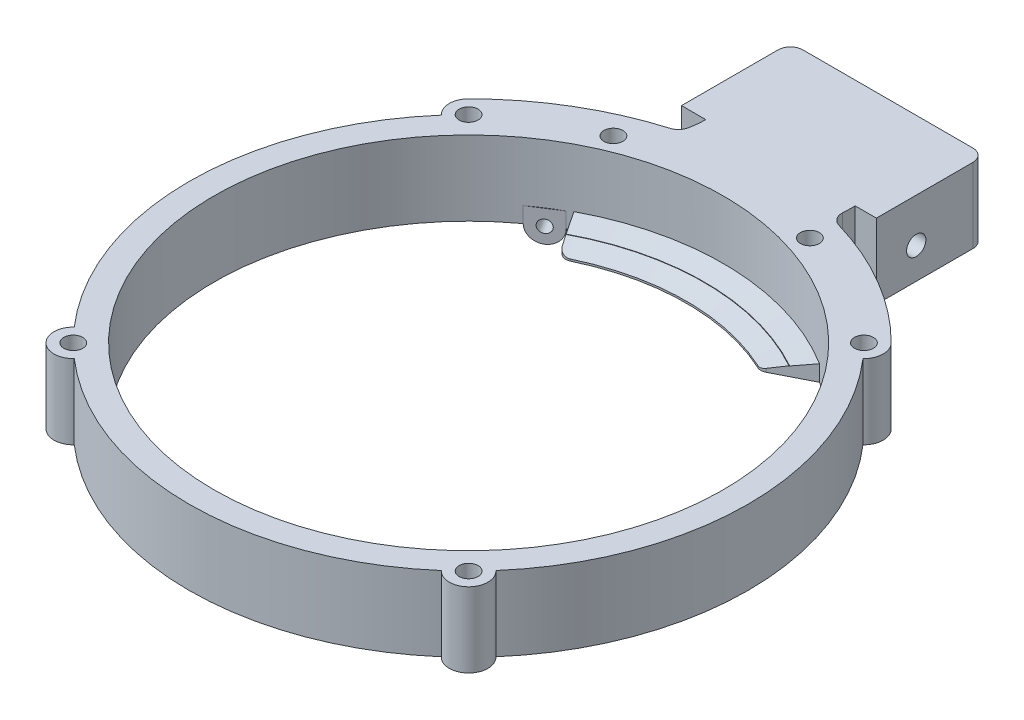
SolidWorks part; units mm, degrees
ref_plane "前视基准面" through (0, 0, 0) normal (0, 0, 1) x (1, 0, 0)
ref_plane "上视基准面" through (0, 0, 0) normal (0, 1, 0) x (1, 0, 0)
ref_plane "右视基准面" through (0, 0, 0) normal (1, 0, 0) x (0, 0, -1)
sketch "草图1" plane through (0, 0, 0) normal (0, 1, 0) x (1, 0, 0)
  line L0 (0, 0) -> (0, 50.1) construction
  line L1 (-12, 50.1) -> (-24, 50.1) construction
  line L2 (12, 50.1) -> (-12, 50.1)
  line L3 (0, 0) -> (12.8351, 41.9818) construction
  line L4 (0, 0) -> (-17.1531, 40.4102) construction
  circle A0 centre (0, 0) radius 40.9
  arc A1 (-13.6688, 46.0127) -> (13.3851, 46.096) centre (0, 0) ccw
  arc A2 (-12.286, 47.4958) -> (-12, 50.1) centre (-24, 50.1) ccw
  arc A3 (-13.6688, 46.0127) -> (-12.286, 47.4958) centre (-14.2383, 47.9298) ccw
  arc A4 (11.9459, 48.1263) -> (12, 50.1) centre (-24, 50.1) ccw
  arc A5 (11.9459, 48.1263) -> (13.3851, 46.096) centre (13.9428, 48.0166) ccw
  circle A6 centre (12.8351, 41.9818) radius 1.525
  circle A7 centre (-17.1531, 40.4102) radius 1.525
  dimension "D1" = 24
  dimension "D2" = 81.8
  dimension "D3" = 96
  dimension "D5" = 2
  dimension "D6" = 12
  dimension "D7" = 2
  dimension "D8" = 17
  dimension "D9" = 3.05
  dimension "D10" = 43.9
  dimension "D4" = 50.1
  dimension "D11" = 40
extrude "凸台-拉伸1" add sketch "草图1" along normal blind 1.5
sketch "草图2" plane through (0, 1.5, 0) normal (0, 1, 0) x (1, 0, 0)
  line L0 (0, 0) -> (0, 40.9) construction
  line L1 (0, 0) -> (-19.2014, 36.1126) construction
  line L2 (0, 0) -> (21.6737, 34.6852) construction
  line L3 (0, 0) -> (15.343, 31.4578) construction
  line L4 (-19.2014, 36.1126) -> (-17.1212, 32.2004)
  line L5 (21.6737, 34.6852) -> (16.0008, 31.7931)
  circle A0 centre (0, 0) radius 35 construction
  circle A1 centre (0, 0) radius 40.9 construction
  arc A2 (21.6737, 34.6852) -> (-19.2014, 36.1126) centre (0, 0) ccw
  arc A3 (-15.1476, 31.5523) -> (14.6899, 31.768) centre (0, 0) cw
  arc A4 (14.6899, 31.768) -> (16.0008, 31.7931) centre (15.3195, 33.1295) ccw
  arc A5 (-15.1476, 31.5523) -> (-17.1212, 32.2004) centre (-15.7968, 32.9046) cw
  point P15 (-16.4315, 30.9032)
  dimension "D1" = 70
  dimension "D5" = 1.5
  dimension "D2" = 28
  dimension "D3" = 60
  dimension "D4" = 6
extrude "凸台-拉伸2" add sketch "草图2" against normal up to surface (1.5 mm away) up to face at (-0.0669, 0, -32.2382)
sketch "草图3" plane through (0, 1.5, 0) normal (0, 1, 0) x (1, 0, 0)
  line L0 (0, 0) -> (0, 44.9) construction
  line L1 (0, 0) -> (31.7491, 31.7491) construction
  circle A0 centre (0, 0) radius 44.9 construction
  circle A1 centre (31.7491, 31.7491) radius 1.525
  circle A2 centre (31.7491, -31.7491) radius 1.525
  circle A3 centre (-31.7491, -31.7491) radius 1.525
  circle A4 centre (-31.7491, 31.7491) radius 1.525
  dimension "D1" = 89.8
  dimension "D3" = 3.05
  dimension "D2" = 45
  dimension "D4" = 4
extrude "切除-拉伸1" cut sketch "草图3" against normal through all both and the other way through all
sketch "草图4" plane through (0, 1.5, 0) normal (0, 1, 0) x (1, 0, 0)
  line L0 (12, 50.1) -> (-12, 50.1) construction
  line L1 (12, 50.1) -> (-12, 50.1)
  line L2 (12, 50.1) -> (-12, 50.1)
  circle A0 centre (0, 0) radius 40.9
  circle A1 centre (-17.1531, 40.4102) radius 1.525
  circle A2 centre (12.8351, 41.9818) radius 1.525
  circle A3 centre (31.7491, 31.7491) radius 1.525
  circle A4 centre (31.7491, -31.7491) radius 1.525
  arc A5 (11.9459, 48.1263) -> (13.3851, 46.096) centre (13.9428, 48.0166) ccw
  arc A6 (11.9459, 48.1263) -> (12, 50.1) centre (-24, 50.1) ccw
  arc A7 (-12.286, 47.4958) -> (-12, 50.1) centre (-24, 50.1) ccw
  arc A8 (-13.6688, 46.0127) -> (-12.286, 47.4958) centre (-14.2383, 47.9298) ccw
  arc A9 (-13.6688, 46.0127) -> (13.3851, 46.096) centre (0, 0) ccw
  arc A10 (11.9459, 48.1263) -> (13.3851, 46.096) centre (13.9428, 48.0166) ccw
  arc A11 (11.9459, 48.1263) -> (12, 50.1) centre (-24, 50.1) ccw
  arc A12 (-12.286, 47.4958) -> (-12, 50.1) centre (-24, 50.1) ccw
  arc A13 (-13.6688, 46.0127) -> (-12.286, 47.4958) centre (-14.2383, 47.9298) ccw
  arc A14 (-13.6688, 46.0127) -> (13.3851, 46.096) centre (0, 0) ccw
  circle A15 centre (-31.7491, -31.7491) radius 1.525
  circle A16 centre (-31.7491, 31.7491) radius 1.525
  dimension "D2" = 3.05
  dimension "D3" = 81.8
  dimension "D1" = 0
extrude "凸台-拉伸3" add sketch "草图4" along normal blind 10.5
sketch "草图5" plane through (0, 12, 0) normal (0, 1, 0) x (1, 0, 0)
  arc A0 (-33.9411, 33.9411) -> (-33.8641, 29.4827) centre (-31.7491, 31.7491) ccw
  arc A1 (33.8641, 29.4827) -> (33.9411, 33.9411) centre (31.7491, 31.7491) ccw
  arc A2 (-33.8641, -29.4827) -> (-29.4827, -33.8641) centre (-31.7491, -31.7491) ccw
  arc A3 (29.4827, -33.8641) -> (33.8641, -29.4827) centre (31.7491, -31.7491) ccw
  arc A4 (-33.8641, 29.4827) -> (-33.8641, -29.4827) centre (0, 0) ccw
  arc A5 (-33.9411, 33.9411) -> (33.9411, 33.9411) centre (0, 0) ccw
  arc A6 (-29.4827, -33.8641) -> (29.4827, -33.8641) centre (0, 0) ccw
  arc A7 (33.8641, -29.4827) -> (33.8641, 29.4827) centre (0, 0) ccw
  arc M8 (-13.6688, 46.0127) -> (13.3851, 46.096) centre (0, 0) ccw
  dimension "D1" = 3.1
extrude "切除-拉伸2" cut sketch "草图5" against normal up to surface (12 mm away) contours A4 A0 A2 M8 | A7 A3 A1 M8 | A6 A2 A3 M8 up to face at (-31.7491, 0, -30.2241)
sketch "草图6" plane through (0, 0, 0) normal (0, -1, 0) x (1, 0, 0)
  line L0 (-20, -35.6765) -> (-24.2038, -32.9695)
  arc A0 (21.6737, -34.6852) -> (-19.2014, -36.1126) centre (0, 0) ccw construction
  arc A1 (-24.2038, -32.9695) -> (-20, -35.6765) centre (0, 0) ccw
  point P0 (-20, -35.6765)
  dimension "D1" = 20
  dimension "D2" = 5
extrude "凸台-拉伸4" add sketch "草图6" against normal blind 2.5
sketch "草图7" plane through (-22.1019, 0, -34.323) normal (0.5414, 0, 0.8408) x (0.8408, 0, -0.5414)
  line L0 (2.5, 0) -> (-2.5, 0) construction
  line L1 (-2.5, 0) -> (2.5, 0)
  arc A0 (-2.5, 0) -> (2.5, 0) centre (0, 0) ccw
extrude "凸台-拉伸5" add sketch "草图7" against normal up to surface (7.1113 mm away) up to face at (-24.1816, 6, -40.6094)
sketch "草图8" plane through (-22.1019, 0, -34.323) normal (0.5414, 0, 0.8408) x (0.8408, 0, -0.5414)
  circle A0 centre (0, 0) radius 1
  dimension "D1" = 2
extrude "切除-拉伸3" cut sketch "草图8" against normal through all
chamfer "倒角1" distance 1.2 angle 67 1 edges at (-0.253, 1.5, -34.9991) first distance on face at (-0.2409, 0.75, -33.3296)
chamfer "倒角2" distance 3 angle 20 1 edges at (1.4274, 1.5, -40.8751) first distance on face at (0.8459, 1.5, -36.8287)
sketch "草图9" plane through (0, 0, -50.1) normal (0, 0, -1) x (-1, 0, 0)
  line L4 (-12, 0) -> (12, 0)
  line L5 (12, 0) -> (12, 12)
  line L6 (12, 12) -> (-12, 12)
  line L7 (-12, 12) -> (-12, 0)
  line L8 (-12, 0) -> (12, 0)
  line L9 (12, 0) -> (12, 12)
  line L10 (12, 12) -> (-12, 12)
  line L11 (-12, 12) -> (-12, 0)
  dimension "D1" = 0
extrude "凸台-拉伸6" add sketch "草图9" along normal blind 17.5
sketch "草图10" plane through (12, 0, 0) normal (1, 0, 0) x (0, 0, -1)
  line L0 (67.6, 12) -> (67.6, 5) construction
  line L1 (67.6, 12) -> (67.6, 0) construction
  line L2 (67.6, 5) -> (56.5, 5) construction
  line L5 (67.6, 12) -> (50.1, 12) construction
  circle A0 centre (56.5, 5) radius 1.55
  dimension "D1" = 3.1
  dimension "D2" = 11.1
  dimension "D3" = 7
extrude "切除-拉伸4" cut sketch "草图10" against normal through all
sketch "草图11" plane through (-12, 0, 0) normal (-1, 0, 0) x (0, 0, 1)
  line L4 (-50.1, 0) -> (-50.1, 12)
  line L5 (-50.1, 12) -> (-67.6, 12)
  line L6 (-67.6, 12) -> (-67.6, 0)
  line L7 (-67.6, 0) -> (-50.1, 0)
  line L8 (-50.1, 0) -> (-50.1, 12)
  line L9 (-50.1, 12) -> (-67.6, 12)
  line L10 (-67.6, 12) -> (-67.6, 0)
  line L11 (-67.6, 0) -> (-50.1, 0)
  circle A1 centre (-56.5, 5) radius 1.55
  dimension "D2" = 3.1
  dimension "D1" = 0
extrude "凸台-拉伸7" add sketch "草图11" along normal blind 3.9
sketch "草图12" plane through (12, 0, 0) normal (1, 0, 0) x (0, 0, -1)
  line L8 (50.1, 12) -> (50.1, 0)
  line L9 (50.1, 0) -> (67.6, 0)
  line L10 (67.6, 0) -> (67.6, 12)
  line L11 (67.6, 12) -> (50.1, 12)
  line L12 (50.1, 12) -> (50.1, 0)
  line L13 (50.1, 0) -> (67.6, 0)
  line L14 (67.6, 0) -> (67.6, 12)
  line L15 (67.6, 12) -> (50.1, 12)
  circle A0 centre (56.5, 5) radius 1.55
  dimension "D2" = 3.1
  dimension "D1" = 0
extrude "凸台-拉伸8" add sketch "草图12" along normal blind 3.4
fillet "圆角1" radius 2 2 edges at (-15.9, 6, -67.6) (15.4, 6, -67.6)
